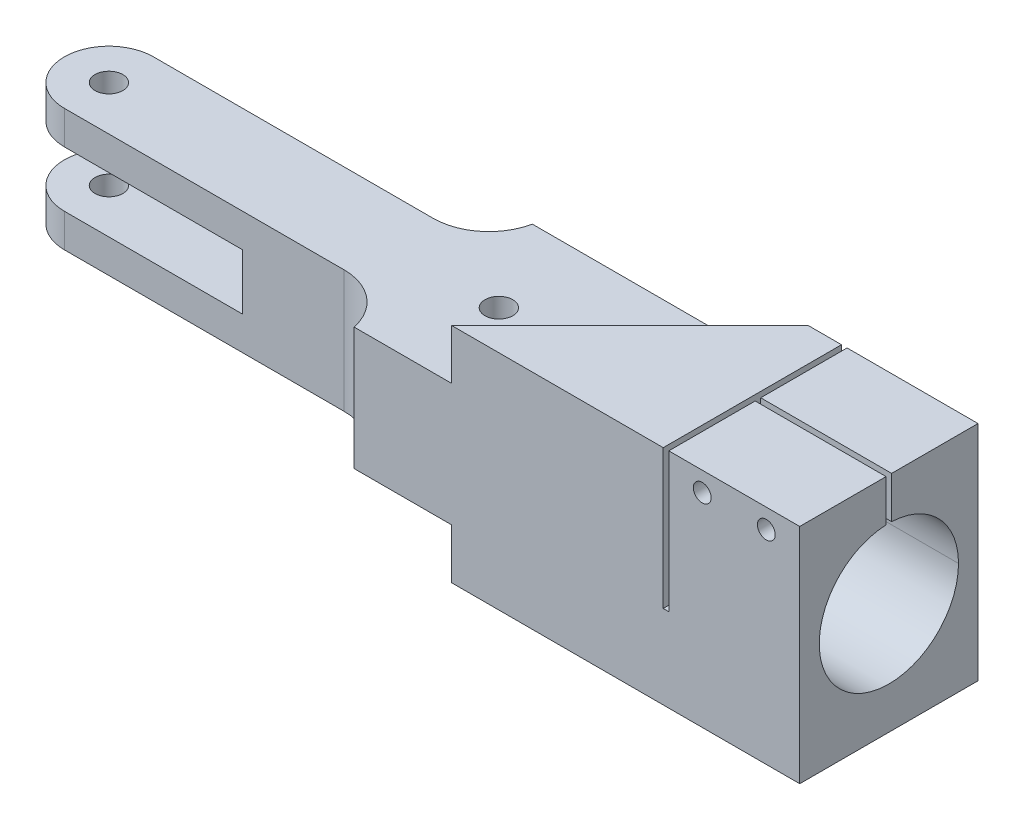
SolidWorks part; units mm, degrees
material "氧化铝"
ref_plane "前视基准面" through (0, 0, 0) normal (0, 0, 1) x (1, 0, 0)
ref_plane "上视基准面" through (0, 0, 0) normal (0, 1, 0) x (1, 0, 0)
ref_plane "右视基准面" through (0, 0, 0) normal (1, 0, 0) x (0, 0, -1)
sketch "草图1" plane through (0, 0, 0) normal (0, 1, 0) x (1, 0, 0)
  line L0 (-60, 8) -> (0, 8)
  line L1 (0, 16) -> (80, 16)
  line L3 (0, -16) -> (80, -16)
  line L4 (80, 16) -> (80, -16)
  line L7 (0, 8) -> (0, 16)
  line L8 (-60, -8) -> (0, -8)
  line L9 (0, -8) -> (0, -16)
  circle A0 centre (-60, 0) radius 2.5
  circle A1 centre (10, 0) radius 2.5
  arc A2 (-60, 8) -> (-60, -8) centre (-60, 0) ccw
  point P0 (0, 0)
  point P2 (80, 0)
  dimension "D4" = 5
  dimension "D5" = 5
  dimension "D1" = 8
  dimension "D2" = 32
  dimension "D3" = 70
  dimension "D6" = 10
  dimension "D7" = 10
  dimension "D8" = 80
extrude "凸台-拉伸1" add sketch "草图1" along normal mid plane 22
fillet "圆角1" radius 10 2 edges at (0, 0, 8) (0, 0, -8)
sketch "草图4" plane through (0, 0, -8) normal (0, 0, -1) x (-1, 0, 0)
  line L0 (68, -11) -> (68, 11) construction
  line L1 (68, 5) -> (28, 5)
  line L2 (68, 5) -> (68, -5)
  line L3 (68, -5) -> (28, -5)
  line L4 (28, 5) -> (28, -5)
  point P6 (28, 0)
  point P8 (68, 0)
  dimension "D1" = 40
  dimension "D2" = 10
extrude "切除-拉伸3" cut sketch "草图4" against normal up to next
sketch "草图6" plane through (0, 0, 0) normal (0, 1, 0) x (1, 0, 0)
  line L0 (80, 16) -> (0, 16) construction
  line L1 (80, 16) -> (49.5, 16)
  line L2 (80, 16) -> (80, -16)
  line L3 (80, -16) -> (17.5, -16)
  line L4 (0, -16) -> (80, -16) construction
  line L6 (80, -16) -> (80, 16) construction
  line L7 (49.5, 16) -> (17.5, -16)
  dimension "D2" = 30.5
  dimension "D1" = 45
extrude "凸台-拉伸2" add sketch "草图6" against normal mid plane 40
sketch "草图7" plane through (80, 0, 0) normal (1, 0, 0) x (0, 0, -1)
  circle A0 centre (0, 0) radius 12.5
  dimension "D1" = 25
extrude "切除-拉伸4" cut sketch "草图7" against normal blind 35
sketch "草图8" plane through (0, 20, 0) normal (0, 1, 0) x (1, 0, 0)
  line L0 (80, -16) -> (80, 16) construction
  line L1 (56, 0.5) -> (80, 0.5)
  line L2 (56, 0.5) -> (56, -0.5)
  line L3 (56, -0.5) -> (80, -0.5)
  line L4 (80, 0.5) -> (80, -0.5)
  line L5 (56, 0.5) -> (80, -0.5) construction
  line L6 (56, -0.5) -> (80, 0.5) construction
  point P0 (68, 0)
  dimension "D1" = 12
  dimension "D2" = 1
extrude "切除-拉伸5" cut sketch "草图8" against normal up to next
sketch "草图9" plane through (0, 20, 0) normal (0, 1, 0) x (1, 0, 0)
  line L0 (56, -0.5) -> (56, 0.5) construction
  line L1 (55.5, 16) -> (56.5, 16)
  line L2 (55.5, 16) -> (55.5, -16)
  line L3 (55.5, -16) -> (56.5, -16)
  line L4 (56.5, 16) -> (56.5, -16)
  line L5 (55.5, 16) -> (56.5, -16) construction
  line L6 (55.5, -16) -> (56.5, 16) construction
  line L7 (17.5, -16) -> (80, -16) construction
  point P0 (56, 0)
  dimension "D1" = 1
extrude "切除-拉伸6" cut sketch "草图9" against normal blind 25
sketch "草图10" plane through (0, 0, -16) normal (0, 0, -1) x (-1, 0, 0)
  line L0 (-80, 20) -> (-80, -20) construction
  line L1 (-56.5, -5) -> (-56.5, 20) construction
  line L2 (-80, 20) -> (-56.5, 20) construction
  circle A0 centre (-74, 16.5) radius 1.6
  circle A1 centre (-62.5, 16.5) radius 1.6
  dimension "D5" = 3.2
  dimension "D6" = 3.2
  dimension "D1" = 6
  dimension "D2" = 6
  dimension "D3" = 3.5
  dimension "D4" = 3.5
extrude "切除-拉伸7" cut sketch "草图10" against normal through all both and the other way through all
